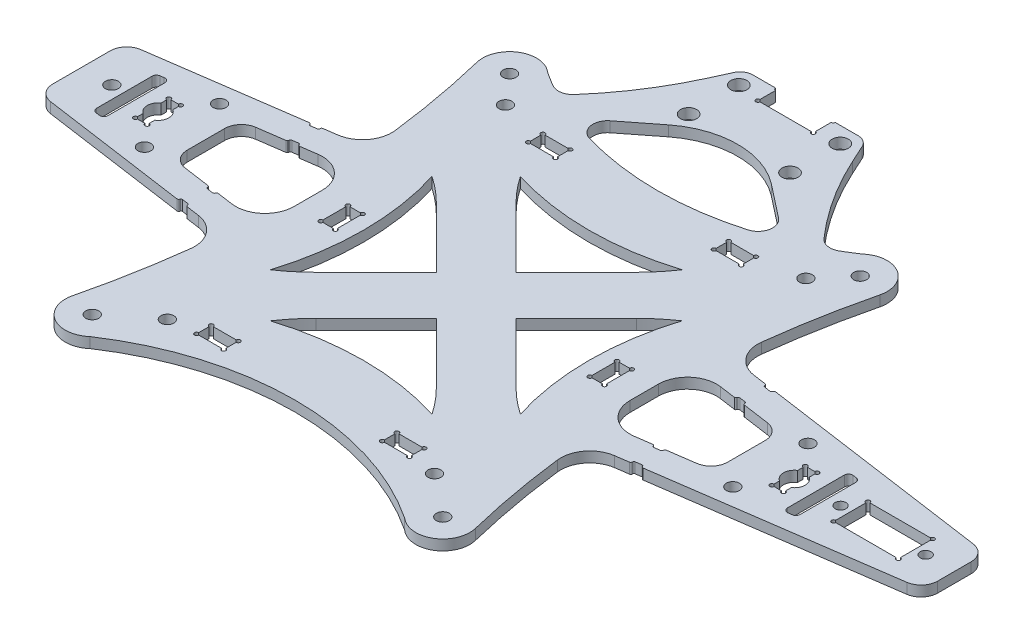
SolidWorks part; units mm, degrees
material "PPS"
ref_plane "前视基准面" through (0, 0, 0) normal (0, 0, 1) x (1, 0, 0)
ref_plane "上视基准面" through (0, 0, 0) normal (0, 1, 0) x (1, 0, 0)
ref_plane "右视基准面" through (0, 0, 0) normal (1, 0, 0) x (0, 0, -1)
sketch "草图1" plane through (0, 0, 0) normal (0, 1, 0) x (1, 0, 0)
  line L3 (-133.7177, 0) -> (146.3754, 0) construction
  line L56 (0, 96.0639) -> (0, -115.1457) construction
  line L65 (-25.5, 41.5) -> (-19, 41.5)
  line L66 (-34, 3.25) -> (-30.5, 3.25)
  line L70 (-34, 3.25) -> (-34, -3.25)
  line L76 (-34, -3.25) -> (-30.5, -3.25)
  line L80 (-30.5, 3.25) -> (-30.5, -3.25)
  line L81 (-25.5, -38) -> (-19, -38)
  line L82 (-25.5, -38) -> (-25.5, -41.5)
  line L83 (-25.5, -41.5) -> (-19, -41.5)
  line L84 (-19, -38) -> (-19, -41.5)
  line L85 (-19, 38) -> (-19, 41.5)
  line L86 (-25.5, 38) -> (-19, 38)
  line L142 (-25.5, 38) -> (-25.5, 41.5)
  line L143 (25.5, 38) -> (25.5, 41.5)
  line L144 (25.5, 38) -> (19, 38)
  line L145 (19, 38) -> (19, 41.5)
  line L146 (19, -38) -> (19, -41.5)
  line L147 (25.5, -41.5) -> (19, -41.5)
  line L148 (25.5, -38) -> (25.5, -41.5)
  line L149 (25.5, -38) -> (19, -38)
  line L150 (30.5, 3.25) -> (30.5, -3.25)
  line L151 (34, -3.25) -> (30.5, -3.25)
  line L152 (34, 3.25) -> (34, -3.25)
  line L153 (34, 3.25) -> (30.5, 3.25)
  line L154 (25.5, 41.5) -> (19, 41.5)
  line L155 (77.65, -2.1518) -> (77.65, -4)
  line L156 (74.85, 4) -> (77.65, 4)
  line L157 (74.85, 4) -> (74.85, 2.1768)
  line L158 (74.85, -4) -> (77.65, -4)
  line L159 (77.65, 4) -> (77.65, 2.1518)
  line L160 (74.85, -2.1768) -> (74.85, -4)
  line L161 (97.5, 7.6653) -> (97.5, -9.1503) construction
  line L162 (89.75, 4.1) -> (105.25, 4.1)
  line L163 (89.75, 4.1) -> (89.75, -4.1)
  line L164 (89.75, -4.1) -> (105.25, -4.1)
  line L165 (105.25, 4.1) -> (105.25, -4.1)
  line L166 (-97.5, 7.6653) -> (-97.5, -9.1503) construction
  line L171 (-74.85, -2.1768) -> (-74.85, -4)
  line L172 (-77.65, 4) -> (-77.65, 2.1518)
  line L173 (-74.85, -4) -> (-77.65, -4)
  line L174 (-74.85, 4) -> (-74.85, 2.1768)
  line L175 (-74.85, 4) -> (-77.65, 4)
  line L176 (-77.65, -2.1518) -> (-77.65, -4)
  line L177 (114.5911, 7.4683) -> (114.5911, -7.4683)
  line L178 (114.5911, 7.4683) -> (43.1936, 17.6463)
  line L179 (114.5911, -7.4683) -> (43.1936, -17.6463)
  line L183 (-23.978, 14.4296) -> (-9.5485, 0)
  line L184 (14.4296, 23.978) -> (0, 9.5485)
  line L185 (-23.978, -14.4296) -> (-9.5485, 0)
  line L186 (-14.4296, 23.978) -> (0, 9.5485)
  line L187 (23.978, -14.4296) -> (9.5485, 0)
  line L188 (23.978, 14.4296) -> (9.5485, 0)
  line L189 (-14.4296, -23.978) -> (0, -9.5485)
  line L190 (14.4296, -23.978) -> (0, -9.5485)
  line L191 (-94.5795, 10.321) -> (-94.5795, -10.321)
  line L192 (-43.1936, 17.6463) -> (-94.5795, 10.321)
  line L193 (-94.5795, -10.321) -> (-43.1936, -17.6463)
  line L195 (-64.75, -7.9571) -> (-64.75, 7.9571)
  line L196 (-64.75, 7.9571) -> (-40.25, 11.4497)
  line L197 (-40.25, 11.4497) -> (-40.25, -11.4497)
  line L198 (-64.75, -7.9571) -> (-40.25, -11.4497)
  line L199 (64.75, 7.9571) -> (40.25, 11.4497)
  line L200 (40.25, 11.4497) -> (40.25, -11.4497)
  line L201 (64.75, -7.9571) -> (40.25, -11.4497)
  line L202 (64.75, 7.9571) -> (64.75, -7.9571)
  line L203 (84.3, 7.5437) -> (81.4, 7.9571)
  line L204 (81.4, 7.9571) -> (81.4, -7.9571)
  line L205 (84.3, -7.5437) -> (81.4, -7.9571)
  line L206 (84.3, 7.5437) -> (84.3, -7.5437)
  line L207 (-84.3, 7.5437) -> (-84.3, -7.5437)
  line L208 (-84.3, -7.5437) -> (-81.4, -7.9571)
  line L209 (-81.4, 7.9571) -> (-81.4, -7.9571)
  line L210 (-84.3, 7.5437) -> (-81.4, 7.9571)
  circle A0 centre (-36, 43) radius 1.55
  circle A1 centre (-32, -42) radius 1.55
  circle A2 centre (32, -42) radius 1.55
  circle A3 centre (36, 43) radius 1.55
  circle A4 centre (42, 50) radius 1.55
  circle A5 centre (42, -50) radius 1.55
  circle A6 centre (-42, -50) radius 1.55
  circle A7 centre (-42, 50) radius 1.55
  arc A8 (74.85, 2.1768) -> (74.85, -2.1768) centre (76.2307, 0) ccw
  arc A9 (77.65, -2.1518) -> (77.65, 2.1518) centre (76.2307, 0) ccw
  circle A10 centre (107.7, 0) radius 1.3
  circle A11 centre (87.3, 0) radius 1.3
  circle A12 centre (-87.3, 0) radius 1.3 construction
  arc A14 (-77.65, -2.1518) -> (-77.65, 2.1518) centre (-76.2307, 0) cw
  arc A15 (-74.85, 2.1768) -> (-74.85, -2.1768) centre (-76.2307, 0) cw
  arc A18 (-37.7098, 54.831) -> (37.7098, 54.831) centre (0, 111.5317) ccw
  arc A20 (48.2756, 48.4632) -> (43.1936, 17.6463) centre (246.1791, 0) ccw
  arc A21 (48.2756, 48.4632) -> (37.7098, 54.831) centre (42, 50) ccw
  arc A22 (-37.7098, -54.831) -> (37.7098, -54.831) centre (0, -111.5317) cw
  arc A23 (48.2756, -48.4632) -> (43.1936, -17.6463) centre (246.1791, 0) cw
  arc A24 (48.2756, -48.4632) -> (37.7098, -54.831) centre (42, -50) cw
  arc A26 (-48.2756, -48.4632) -> (-37.7098, -54.831) centre (-42, -50) ccw
  arc A27 (-48.2756, -48.4632) -> (-43.1936, -17.6463) centre (-246.1791, 0) ccw
  arc A28 (-48.2756, 48.4632) -> (-37.7098, 54.831) centre (-42, 50) cw
  arc A30 (-48.2756, 48.4632) -> (-43.1936, 17.6463) centre (-246.1791, 0) cw
  arc A31 (-23.978, 14.4296) -> (-29.9602, 19.3706) centre (-52.8883, -14.4807) ccw
  arc A32 (-23.978, -14.4296) -> (-29.9602, -19.3706) centre (-52.8883, 14.4807) cw
  arc A33 (-29.9602, -19.3706) -> (-29.9602, 19.3706) centre (-91.9966, 0) ccw
  arc A34 (-14.4296, 23.978) -> (-19.3706, 29.9602) centre (14.4807, 52.8883) cw
  arc A35 (-19.3706, 29.9602) -> (19.3706, 29.9602) centre (0, 91.9966) ccw
  arc A36 (14.4296, 23.978) -> (19.3706, 29.9602) centre (-14.4807, 52.8883) ccw
  arc A37 (23.978, 14.4296) -> (29.9602, 19.3706) centre (52.8883, -14.4807) cw
  arc A38 (29.9602, 19.3706) -> (29.9602, -19.3706) centre (91.9966, 0) ccw
  arc A39 (23.978, -14.4296) -> (29.9602, -19.3706) centre (52.8883, 14.4807) ccw
  arc A40 (14.4296, -23.978) -> (19.3706, -29.9602) centre (-14.4807, -52.8883) cw
  arc A41 (19.3706, -29.9602) -> (-19.3706, -29.9602) centre (0, -91.9966) ccw
  arc A42 (-14.4296, -23.978) -> (-19.3706, -29.9602) centre (14.4807, -52.8883) ccw
  circle A43 centre (70.5, 9) radius 1.55
  circle A44 centre (70.5, -9) radius 1.55
  circle A45 centre (-70.5, -9) radius 1.55
  circle A46 centre (-70.5, 9) radius 1.55
  circle A47 centre (-87.3, 0) radius 1.55
  point P81 (-34, 0)
  point P118 (0, 0)
  point P140 (-40.25, 0)
  point P149 (-64.75, 0)
  dimension "D5" = 38
  dimension "D18" = 8.2
  dimension "D24" = 3.1
  dimension "D6" = 3.1
  dimension "D11" = 50
  dimension "D15" = 74.85
  dimension "D16" = 2.6
  dimension "D17" = 15.5
  dimension "D21" = 3.1
  dimension "D1" = 6.5
  dimension "D2" = 3.5
  dimension "D3" = 30.5
  dimension "D4" = 19
  dimension "D7" = 32
  dimension "D8" = 42
  dimension "D9" = 43
  dimension "D10" = 36
  dimension "D12" = 42
  dimension "D13" = 2.8
  dimension "D14" = 4
  dimension "D19" = 2.45
  dimension "D20" = 97.5
  dimension "D22" = 9
  dimension "D23" = 70.5
  dimension "D25" = 6.55
  dimension "D26" = 5.75
  dimension "D27" = 6.25
  dimension "D28" = 4
  dimension "D29" = 2.45
  dimension "D30" = 3
  dimension "D31" = 3.75
extrude "凸台-拉伸1" add sketch "草图1" along normal blind 2.5
fillet "圆角1" radius 4 8 edges at (114.5911, 1.25, -7.4683) (114.5911, 1.25, 7.4683) (-94.5795, 1.25, 10.321) (-94.5795, 1.25, -10.321) (-64.75, 1.25, 7.9571) (-64.75, 1.25, -7.9571) (64.75, 1.25, 7.9571) (64.75, 1.25, -7.9571)
fillet "圆角2" radius 7 8 edges at (43.1936, 1.25, -17.6463) (43.1936, 1.25, 17.6463) (-43.1936, 1.25, 17.6463) (-43.1936, 1.25, -17.6463) (40.25, 1.25, 11.4497) (40.25, 1.25, -11.4497) (-40.25, 1.25, 11.4497) (-40.25, 1.25, -11.4497)
sketch "草图6" plane through (0, 2.5, 0) normal (0, 1, 0) x (1, 0, 0)
  line L0 (53.296, 16.2062) -> (55.6373, 15.8724)
  line L1 (111.1557, 7.958) -> (49.8638, 16.6954) construction
  line L2 (55.6373, 15.8724) -> (55.2455, 15.2717)
  line L3 (55.2455, 15.2717) -> (53.296, 15.5496)
  line L4 (53.296, 15.5496) -> (53.296, 16.2062)
  line L5 (56.9219, 15.6893) -> (55.9975, 9.2048) construction
  line L6 (61.3145, 8.4469) -> (48.2379, 10.311) construction
  line L7 (56.4597, 12.447) -> (48.7761, 13.5424) construction
  line L8 (54.5046, 10.0742) -> (52.555, 10.3521)
  line L9 (54.7129, 9.3879) -> (54.5046, 10.0742)
  line L10 (52.3716, 9.7217) -> (54.7129, 9.3879)
  line L11 (52.555, 10.3521) -> (52.3716, 9.7217)
  line L12 (0, 0) -> (132.6638, 0) construction
  line L13 (52.555, -10.3521) -> (52.3716, -9.7217)
  line L14 (52.3716, -9.7217) -> (54.7129, -9.3879)
  line L15 (54.7129, -9.3879) -> (54.5046, -10.0742)
  line L16 (54.5046, -10.0742) -> (52.555, -10.3521)
  line L17 (53.296, -15.5496) -> (53.296, -16.2062)
  line L18 (55.2455, -15.2717) -> (53.296, -15.5496)
  line L19 (55.6373, -15.8724) -> (55.2455, -15.2717)
  line L20 (53.296, -16.2062) -> (55.6373, -15.8724)
  line L21 (0, -0.7474) -> (0, 57.4396) construction
  line L22 (-53.296, -16.2062) -> (-55.6373, -15.8724)
  line L23 (-55.6373, -15.8724) -> (-55.2455, -15.2717)
  line L24 (-55.2455, -15.2717) -> (-53.296, -15.5496)
  line L25 (-53.296, -15.5496) -> (-53.296, -16.2062)
  line L26 (-54.5046, -10.0742) -> (-52.555, -10.3521)
  line L27 (-54.7129, -9.3879) -> (-54.5046, -10.0742)
  line L28 (-52.3716, -9.7217) -> (-54.7129, -9.3879)
  line L29 (-52.555, -10.3521) -> (-52.3716, -9.7217)
  line L30 (-52.555, 10.3521) -> (-52.3716, 9.7217)
  line L31 (-52.3716, 9.7217) -> (-54.7129, 9.3879)
  line L32 (-54.7129, 9.3879) -> (-54.5046, 10.0742)
  line L33 (-54.5046, 10.0742) -> (-52.555, 10.3521)
  line L34 (-53.296, 15.5496) -> (-53.296, 16.2062)
  line L35 (-55.2455, 15.2717) -> (-53.296, 15.5496)
  line L36 (-55.6373, 15.8724) -> (-55.2455, 15.2717)
  line L37 (-53.296, 16.2062) -> (-55.6373, 15.8724)
  dimension "D1" = 65
  dimension "D2" = 0.65
extrude "切除-拉伸3" cut sketch "草图6" against normal through all
fillet "圆角5" radius 0.35 32 edges at (-55.6373, 1.25, -15.8724) (-55.2455, 1.25, -15.2717) (-53.296, 1.25, -15.5496) (-53.296, 1.25, -16.2062) (-52.3716, 1.25, 9.7217) (-52.555, 1.25, 10.3521) (-54.5046, 1.25, 10.0742) (-54.7129, 1.25, 9.3879) (-52.3716, 1.25, -9.7217) (-52.555, 1.25, -10.3521) (-54.7129, 1.25, -9.3879) (-54.5046, 1.25, -10.0742) (-53.296, 1.25, 16.2062) (-53.296, 1.25, 15.5496) (-55.2455, 1.25, 15.2717) (-55.6373, 1.25, 15.8724) (55.6373, 1.25, 15.8724) (55.2455, 1.25, 15.2717) (53.296, 1.25, 15.5496) (53.296, 1.25, 16.2062) (54.7129, 1.25, 9.3879) (54.5046, 1.25, 10.0742) (52.555, 1.25, 10.3521) (52.3716, 1.25, 9.7217) (54.7129, 1.25, -9.3879) (54.5046, 1.25, -10.0742) (52.3716, 1.25, -9.7217) (52.555, 1.25, -10.3521) (55.2455, 1.25, -15.2717) (53.296, 1.25, -15.5496) (55.6373, 1.25, -15.8724) (53.296, 1.25, -16.2062)
fillet "圆角4" radius 1 8 edges at (-81.4, 1.25, 7.9571) (-84.3, 1.25, 7.5437) (-84.3, 1.25, -7.5437) (-81.4, 1.25, -7.9571) (81.4, 1.25, 7.9571) (84.3, 1.25, 7.5437) (84.3, 1.25, -7.5437) (81.4, 1.25, -7.9571)
sketch "光流接口-修改" plane through (0, 0, 0) normal (0, 1, 0) x (1, 0, 0)
  line L0 (30.4025, 52.8577) -> (32.0373, 51.0287)
  line L1 (-32.0373, 51.0287) -> (-30.4025, 52.8577)
  line L2 (-6.65, 78.8853) -> (-6.65, 74.1353)
  line L3 (-6.65, 74.1353) -> (-0.15, 74.1353)
  line L4 (-0.15, 74.1353) -> (-0.15, 78.8853) construction
  line L5 (-12.6234, 78.8853) -> (-6.65, 78.8853)
  line L6 (-0.15, 74.1353) -> (0.15, 74.1353)
  line L7 (6.65, 74.1353) -> (0.15, 74.1353)
  line L8 (0.15, 74.1353) -> (0.15, 78.8853) construction
  line L9 (6.65, 78.8853) -> (6.65, 74.1353)
  line L10 (12.6234, 78.8853) -> (6.65, 78.8853)
  line L12 (12.3359, 58.409) -> (29.4648, 44.9866)
  line L13 (15.3497, 77.1372) -> (17.348, 72.7857)
  line L14 (0, -39.4607) -> (0, 39.4607) construction
  line L15 (-15.3497, 77.1372) -> (-17.348, 72.7857)
  line L16 (-12.3359, 58.409) -> (-29.4648, 44.9866)
  line L17 (-12.6234, 78.8853) -> (12.6234, 78.8853) construction
  circle A38 centre (-12.15, 75.08) radius 1.925
  circle A39 centre (-12.15, 63.05) radius 1.925
  circle A40 centre (12.15, 63.05) radius 1.925
  circle A41 centre (12.15, 75.08) radius 1.925
  circle A42 centre (-36, 43) radius 1.55
  circle A43 centre (36, 43) radius 1.55
  arc A44 (-37.8248, 46.5595) -> (-32.3705, 41.3187) centre (-36, 43) ccw
  arc A45 (37.8248, 46.5595) -> (32.3705, 41.3187) centre (36, 43) cw
  arc A46 (32.3705, 41.3187) -> (29.4648, 44.9866) centre (23.2968, 37.1154) ccw
  arc A47 (37.8248, 46.5595) -> (32.0373, 51.0287) centre (46.9489, 64.357) cw
  arc A48 (-12.3359, 58.409) -> (12.3359, 58.409) centre (0, 42.6665) cw
  arc A49 (17.348, 72.7857) -> (30.4025, 52.8577) centre (90.0489, 106.1709) ccw
  arc A50 (12.6234, 78.8853) -> (15.3497, 77.1372) centre (12.6234, 75.8853) cw
  arc A51 (-12.6234, 78.8853) -> (-15.3497, 77.1372) centre (-12.6234, 75.8853) ccw
  arc A52 (-17.348, 72.7857) -> (-30.4025, 52.8577) centre (-90.0489, 106.1709) cw
  arc A53 (-37.8248, 46.5595) -> (-32.0373, 51.0287) centre (-46.9489, 64.357) ccw
  arc A54 (-32.3705, 41.3187) -> (-29.4648, 44.9866) centre (-23.2968, 37.1154) cw
  arc A55 (-37.8248, 46.5595) -> (-32.3705, 41.3187) centre (-36, 43) ccw
  circle A56 centre (-36, 43) radius 1.55
  point P10 (0, 78.8853)
  dimension "D4" = 3.85
  dimension "D1" = 12.03
  dimension "D2" = 24.3
  dimension "D3" = 63.05
  dimension "D5" = 5.5
  dimension "D6" = 6.5
  dimension "D7" = 4.75
extrude "凸台-拉伸2" add sketch "光流接口-修改" along normal up to surface (2.5 mm away) from surface contours A48 L14 L17 A51 L15 A52 L1 A53 A44 A54 L16 A42 A39 A38 | L14 A48 L12 A46 A45 A47 L0 A49 L13 A50 L17 A40 A41 A43 region at (30.5534, 0, -51.3475) up to face at (53.4999, 2.5, 0) starting at face at (53.4999, 0, 0)
sketch "草图10" plane through (0, 0, 0) normal (0, 1, 0) x (1, 0, 0)
  line L0 (0, 0) -> (0, -66.7571) construction
  line L1 (-6.65, 74.1353) -> (6.65, 74.1353) construction
  circle A0 centre (-77.65, 4) radius 0.5
  circle A1 centre (-74.85, 4) radius 0.5
  circle A2 centre (-77.65, -4) radius 0.5
  circle A3 centre (-74.85, -4) radius 0.5
  circle A4 centre (-25.5, 41.5) radius 0.5
  circle A5 centre (-19, 41.5) radius 0.5
  circle A6 centre (-25.5, 38) radius 0.5
  circle A7 centre (-19, 38) radius 0.5
  circle A8 centre (-34, 3.25) radius 0.5
  circle A9 centre (-30.5, 3.25) radius 0.5
  circle A10 centre (-34, -3.25) radius 0.5
  circle A11 centre (-30.5, -3.25) radius 0.5
  circle A12 centre (-25.5, -38) radius 0.5
  circle A13 centre (-19, -38) radius 0.5
  circle A14 centre (-25.5, -41.5) radius 0.5
  circle A15 centre (-19, -41.5) radius 0.5
  circle A16 centre (19, -41.5) radius 0.5
  circle A17 centre (25.5, -41.5) radius 0.5
  circle A18 centre (19, -38) radius 0.5
  circle A19 centre (25.5, -38) radius 0.5
  circle A20 centre (30.5, -3.25) radius 0.5
  circle A21 centre (34, -3.25) radius 0.5
  circle A22 centre (30.5, 3.25) radius 0.5
  circle A23 centre (34, 3.25) radius 0.5
  circle A24 centre (19, 38) radius 0.5
  circle A25 centre (25.5, 38) radius 0.5
  circle A26 centre (19, 41.5) radius 0.5
  circle A27 centre (25.5, 41.5) radius 0.5
  circle A28 centre (74.85, -4) radius 0.5
  circle A29 centre (77.65, -4) radius 0.5
  circle A30 centre (74.85, 4) radius 0.5
  circle A31 centre (77.65, 4) radius 0.5
  circle A32 centre (89.75, 4.1) radius 0.5
  circle A33 centre (105.25, 4.1) radius 0.5
  circle A34 centre (89.75, -4.1) radius 0.5
  circle A35 centre (105.25, -4.1) radius 0.5
  circle A37 centre (-6.65, 74.1353) radius 0.5
  circle A38 centre (6.65, 74.1353) radius 0.5
  circle A39 centre (-6.65, 78.8853) radius 0.5
  circle A40 centre (6.65, 78.8853) radius 0.5
  dimension "D1" = 1
extrude "切除-拉伸6" cut sketch "草图10" along normal through all
fillet "圆角6" radius 3.5 4 edges at (31.7859, 1.25, -51.31) (25.2489, 1.25, -48.2902) (-31.7859, 1.25, -51.31) (-25.2489, 1.25, -48.2902)
